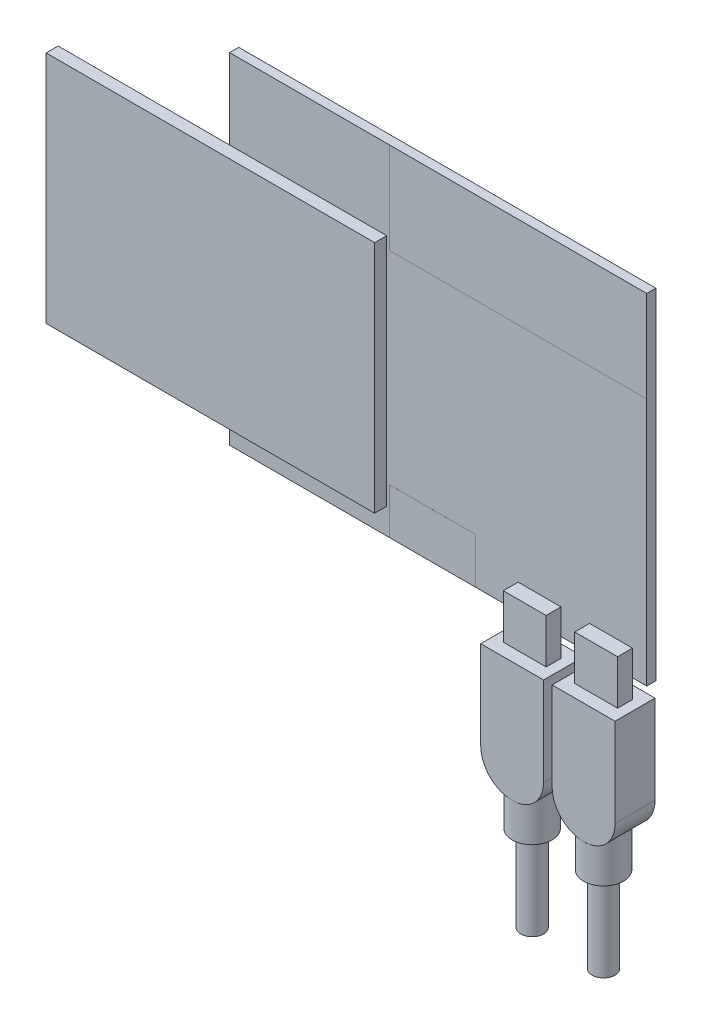
SolidWorks part; units mm, degrees
note: '?' marks a value the reader was unsure of.
ref_plane "Front Plane" through (0, 0, 0) normal (0, 0, 1) x (1, 0, 0)
ref_plane "Top Plane" through (0, 0, 0) normal (0, 1, 0) x (1, 0, 0)
ref_plane "Right Plane" through (0, 0, 0) normal (1, 0, 0) x (0, 0, -1)
sketch "Sketch1" plane through (0, 0, 0) normal (0, 0, 1) x (1, 0, 0)
  line L1 (0, 0) -> (-73, 0)
  line L2 (0, 0) -> (0, 59.5)
  line L3 (0, 59.5) -> (-73, 59.5)
  line L4 (-73, 0) -> (-73, 59.5)
  dimension "D1" = 59.5
  dimension "D2" = 73
extrude "Green PCB" add sketch "Sketch1" along normal blind 1.6
sketch "Sketch2" plane through (0, 0, 1.6) normal (0, 0, 1) x (1, 0, 0)
  line L0 (-73, 59.5) -> (-73, 0) construction
  line L1 (-103, 45.5) -> (-45.5, 45.5)
  line L2 (-103, 45.5) -> (-103, 4.5)
  line L3 (-103, 4.5) -> (-45.5, 4.5)
  line L4 (-45.5, 45.5) -> (-45.5, 4.5)
  line L5 (-73, 0) -> (0, 0) construction
  line L6 (-88.25, 4.5) -> (-88.25, 45.5) construction
  dimension "D1" = 41
  dimension "D2" = 57.5
  dimension "D3" = 30
  dimension "D4" = 4.5
  dimension "D5" = 14.75
extrude "Blue PCB" add sketch "Sketch2" along normal blind 2.1
ref_plane "Between Antennas" through (0, 25, 0) normal (0, -1, 0) x (-1, 0, 0)
ref_plane "Antenna Plane" through (-88.25, 0, 0) normal (-1, 0, 0) x (0, 0, 1)
ref_axis "Axis1" through (-88.25, 25, -9.3549) along (0, 0, 1)?
ref_point "PDoA Origin"
sketch "Sketch3" plane through (0, 0, 1.6) normal (0, 0, 1) x (1, 0, 0)
  line L1 (0, 59.5) -> (-45, 59.5)
  line L2 (0, 59.5) -> (0, 43.5)
  line L3 (0, 43.5) -> (-45, 43.5)
  line L4 (-45, 59.5) -> (-45, 43.5)
  line L5 (-45, 0) -> (-30, 0)
  line L6 (-45, 0) -> (-45, 8)
  line L7 (-45, 8) -> (-30, 8)
  line L8 (-30, 0) -> (-30, 8)
  line L10 (0, 0) -> (0, 59.5) construction
  dimension "D1" = 45
  dimension "D2" = 16
  dimension "D3" = 15
  dimension "D4" = 30
  dimension "D5" = 8
extrude "Clamp Area" add sketch "Sketch3" along normal blind 0.001
sketch "Sketch4" plane through (0, 0, 1.6) normal (0, 0, 1) x (1, 0, 0)
  line L0 (0, 0) -> (0, 43.5) construction
  line L1 (-10, 4.5) -> (-2.5, 4.5)
  line L2 (-10, 4.5) -> (-10, -3.3)
  line L3 (-10, -3.3) -> (-2.5, -3.3)
  line L4 (-2.5, 4.5) -> (-2.5, -3.3)
  line L5 (-73, 0) -> (-45, 0) construction
  dimension "D1" = 7.5
  dimension "D2" = 7.8
  dimension "D3" = 2.5
  dimension "D4" = 3.3
extrude "USB Port" add sketch "Sketch4" along normal blind 2.6
ref_plane "Plane1" through (0, 0, 2.9) normal (0, 0, 1) x (1, 0, 0)
sketch "Sketch5" plane through (0, 0, 2.9) normal (0, 0, 1) x (1, 0, 0)
  line L0 (-11.75, -3.3) -> (-0.75, -3.3)
  line L1 (-0.75, -3.3) -> (-0.75, -18.8)
  line L2 (-11.75, -3.3) -> (-11.75, -18.8)
  line L3 (-10, -3.3) -> (-2.5, -3.3) construction
  arc A0 (-11.75, -18.8) -> (-0.75, -18.8) centre (-6.25, -18.8) ccw
  point P5 (-6.25, -3.3)
  point P10 (-6.25, -3.3)
  dimension "D1" = 11
  dimension "D2" = 21
extrude "USB Body" add sketch "Sketch5" along normal mid plane 7
ref_plane "Plane2" through (0, -24.3, 0) normal (0, -1, 0) x (-1, 0, 0)
sketch "Sketch7" plane through (0, -24.3, 0) normal (0, -1, 0) x (-1, 0, 0)
  line L0 (0.75, -6.4) -> (11.75, -6.4) construction
  line L1 (11.75, 0.6) -> (0.75, 0.6) construction
  line L2 (6.25, -6.4) -> (6.25, 0.6) construction
  circle A0 centre (6.25, -2.9) radius 3.5
  point P8 (6.25, 0.6)
  point P12 (6.25, -6.4)
  point P14 (6.25, -2.9)
extrude "USB Tension Relief" add sketch "Sketch7" along normal blind 6 and the other way up to next (6 mm away)
sketch "Sketch8" plane through (0, -30.3, 0) normal (0, -1, 0) x (1, 0, 0)
  circle A0 centre (-6.25, 2.9) radius 2
  dimension "D1" = 4
extrude "USB Cord" add sketch "Sketch8" along normal blind 15
sketch "Sketch9" plane through (0, 0, 1.6) normal (0, 0, -1) x (-1, 0, 0)
  line L0 (103, 45.5) -> (103, 4.5) construction
  line L1 (88.2, 35.25) -> (88.2, 14.75) construction
  line L2 (88.2, 25) -> (103, 25) construction
  line L3 (85.0666, 38.1213) -> (89.3893, 36.5479)
  line L4 (89.3893, 36.5479) -> (91.3334, 32.3787)
  line L5 (91.3334, 32.3787) -> (87.0107, 33.9521)
  line L6 (87.0107, 33.9521) -> (85.0666, 38.1213)
  line L11 (87.2279, 37.3346) -> (89.1721, 33.1654) construction
  circle A0 centre (88.2, 35.25) radius 5.5
  point P20 (88.2, 35.25)
  dimension "D2" = 11
  dimension "D3" = 14.8
  dimension "D1" = 20.5
  dimension "D4" = 45
  dimension "D5" = 8.5
  dimension "D6" = 70
extrude "Mona Lisa Antenna" add sketch "Sketch9" along normal blind 0.001
pattern_linear "LPattern1" count 2 spacing 20.5 along (0, -1, 0) of "Mona Lisa Antenna"
pattern_linear "LPattern2" count 2 spacing 12.5 along (-1, 0, 0) of "USB Port", "USB Body", "USB Tension Relief", "USB Cord"
